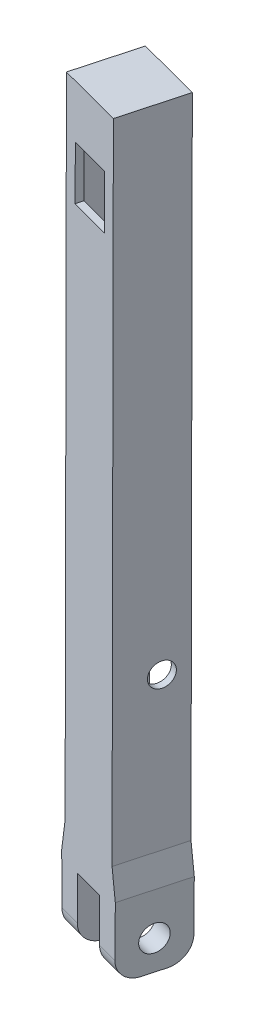
SolidWorks part; units mm, degrees
ref_plane "Alzado" through (0, 0, 0) normal (0, 0, 1) x (1, 0, 0)
ref_plane "Planta" through (0, 0, 0) normal (0, 1, 0) x (1, 0, 0)
ref_plane "Vista lateral" through (0, 0, 0) normal (1, 0, 0) x (0, 0, -1)
sketch "Sketch1" plane through (-8.5501, 0.1505, 31.9099) normal (-0.2588, 0.0046, 0.9659) x (0.9659, 0.005, 0.2588)
  line L0 (-2.1167, -0.0004) -> (-5.1167, -0.0004)
  line L1 (0.0833, -0.0086) -> (0.0833, 10.8169) construction
  line L2 (-5.1167, -0.0004) -> (-5.2081, 9.9992)
  line L3 (-5.2081, 9.9992) -> (-4.5496, 13.9446)
  line L4 (0.0833, -0.0086) -> (14.7101, -0.0086) construction
  line L6 (-2.1167, -0.0004) -> (-2.1167, 8.9996)
  line L29 (-4.5496, 13.9446) -> (-4.5496, 103.9446)
  line L37 (2.2833, -0.0004) -> (5.2833, -0.0004)
  line L38 (5.2833, -0.0004) -> (5.3748, 9.9992)
  line L39 (2.2833, -0.0004) -> (2.2833, 8.9996)
  line L40 (5.3748, 9.9992) -> (4.7162, 13.9446)
  line L41 (4.7162, 13.9446) -> (4.7162, 103.9446)
  line L42 (-2.1167, 8.9996) -> (2.2833, 8.9996)
  line L43 (-4.5496, 103.9446) -> (4.7162, 103.9446)
  point P14 (0.0833, 8.9795)
  dimension "D1" = 3
  dimension "D2" = 90
  dimension "D3" = 2.2
  dimension "D4" = 9
  dimension "D5" = 10
  dimension "D6" = 170
  dimension "D7" = 4
  dimension "D8" = 90
  dimension "D9" = 90
  dimension "D10" = 90
extrude "Boss-Extrude1" add sketch "Sketch1" against normal blind 9
sketch "Sketch2" plane through (-2.0445, -0.0106, -0.5478) normal (0.9659, 0.005, 0.2588) x (0.2588, -0.0054, -0.9659)
  line L3 (-33.0359, -0.0287) -> (-33.0436, 8.9713) construction
  line L4 (-24.0359, -0.021) -> (-33.0359, -0.0287) construction
  circle A0 centre (-28.5394, 4.1002) radius 1.8
  dimension "D1" = 3.6
  dimension "D2" = 4.5
  dimension "D3" = 4.125
extrude "Cut-Extrude1" cut sketch "Sketch2" along normal mid plane 23
shell "Shell1" thickness 1 removed face at (-6.2235, 22.9239, 23.1084)
fillet "Fillet3" radius 3 4 edges at (-12.0436, 0.132, 30.974) (-9.7142, 0.091, 22.2807) (-2.5664, 0.128, 24.1958) (-4.8958, 0.169, 32.889)
sketch "Sketch4" plane through (4.5555, 0.0236, 1.2205) normal (0.9659, 0.005, 0.2588) x (0.2588, 0.0013, -0.9659)
  line L0 (-23.9533, 14.086) -> (-23.4229, 104.0845) construction
  line L3 (-27.0354, 0.1589) -> (-30.0354, 0.1766) construction
  circle A0 centre (-27.0323, 34.6212) radius 1.6
  dimension "D1" = 3.2
  dimension "D2" = 3.2
  dimension "D3" = 34.4617
sketch "Sketch5" plane through (4.5555, 0.0236, 1.2205) normal (0.9659, 0.005, 0.2588) x (0.2588, 0.0013, -0.9659)
  circle A1 centre (-27.1806, 35.2356) radius 1.65
extrude "Cut-Extrude4" cut sketch "Sketch5" against normal blind 16
sketch "Sketch6" plane through (-8.5501, 0.1505, 31.9099) normal (-0.2588, 0.0046, 0.9659) x (0.9659, 0.0012, 0.2588)
  line L5 (-0.3052, 102.9442) -> (-0.1673, 76.7229) construction
  line L6 (3.3277, 102.9579) -> (-3.938, 102.9305) construction
  line L8 (-3.133, 96.5454) -> (2.6288, 96.5454)
  line L9 (-3.133, 96.5454) -> (-3.133, 89.1454)
  line L10 (-3.133, 89.1454) -> (2.6288, 89.1454)
  line L11 (2.6288, 96.5454) -> (2.6288, 89.1454)
  line L12 (-3.133, 96.5454) -> (2.6288, 89.1454) construction
  line L13 (-3.133, 89.1454) -> (2.6288, 96.5454) construction
  point P4 (-0.2521, 92.8454)
  dimension "D1" = 7.4
extrude "Cut-Extrude5" cut sketch "Sketch6" against normal blind 3
